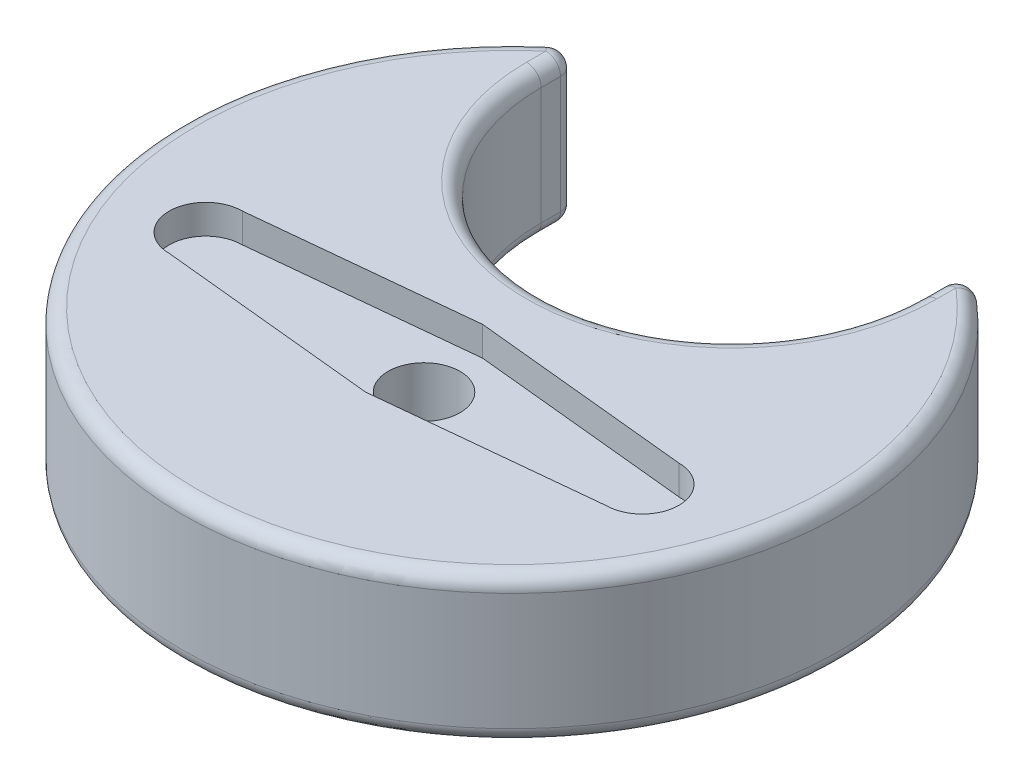
SolidWorks part; units mm, degrees
ref_plane "Front Plane" through (0, 0, 0) normal (0, 0, 1) x (1, 0, 0)
ref_plane "Top Plane" through (0, 0, 0) normal (0, 1, 0) x (1, 0, 0)
ref_plane "Right Plane" through (0, 0, 0) normal (1, 0, 0) x (0, 0, -1)
sketch "Sketch2" plane through (0, 0, 0) normal (0, 1, 0) x (1, 0, 0)
  line L0 (0, -22.5) -> (0, 22.5) construction
  line L5 (-13, 15) -> (-13, 16.3172)
  line L6 (13, 15) -> (13, 16.3172)
  arc A4 (-14.6512, 17.0761) -> (14.6512, 17.0761) centre (0, 0) ccw
  arc A5 (-13, 15) -> (13, 15) centre (0, 15) ccw
  arc A8 (-13, 16.3172) -> (-14.6512, 17.0761) centre (-14, 16.3172) ccw
  arc A9 (13, 16.3172) -> (14.6512, 17.0761) centre (14, 16.3172) cw
  point P6 (0, 0)
  point P7 (0, 0)
  point P17 (-14.6512, 17.0761)
  dimension "D3" = 13
  dimension "D2" = 45
  dimension "D1" = 13
  dimension "D4" = 15
  dimension "D5" = 1
extrude "Boss-Extrude1" add sketch "Sketch2" along normal blind 10
sketch "Sketch4" plane through (0, 10, 0) normal (0, 1, 0) x (1, 0, 0)
  line L0 (0, -6) -> (-14.9, -6) construction
  line L1 (0, -6) -> (14.9, -6) construction
  line L2 (0, -6) -> (0, -2) construction
  line L3 (-14.9, -3.5) -> (0, -2)
  line L4 (0, -2) -> (14.9, -3.5)
  line L5 (0, -10) -> (14.9, -8.5)
  line L6 (-14.9, -8.5) -> (0, -10)
  arc A0 (-14.9, -3.5) -> (-14.9, -8.5) centre (-14.9, -6) ccw
  arc A1 (14.9, -8.5) -> (14.9, -3.5) centre (14.9, -6) ccw
  circle A3 centre (0, -6) radius 2.4523
  point P5 (0, -2)
  dimension "D1" = 5
  dimension "D5" = 4.9047
  dimension "D2" = 14.9
  dimension "D3" = 14.9
  dimension "D4" = 4
  dimension "D6" = 6
extrude "Cut-Extrude2" cut sketch "Sketch4" against normal blind 2
extrude "Cut-Extrude3" cut sketch "Sketch4<2>" against normal through all contours A3 region at (0, 10, 6)
sketch "Sketch4<2>" plane through (0, 10, 0) normal (0, 1, 0) x (1, 0, 0) same geometry as "Sketch4"
fillet "Fillet2" radius 1 12 edges at (0, 0, 22.5) (0, 10, 22.5) (0, 0, -2) (13, 0, -15.6586) (0, 10, -2) (13, 10, -15.6586) (-13, 0, -15.6586) (-13.5824, 0, -17.2258) (13.5824, 0, -17.2258) (-13, 10, -15.6586) (-13.5824, 10, -17.2258) (13.5824, 10, -17.2258)
